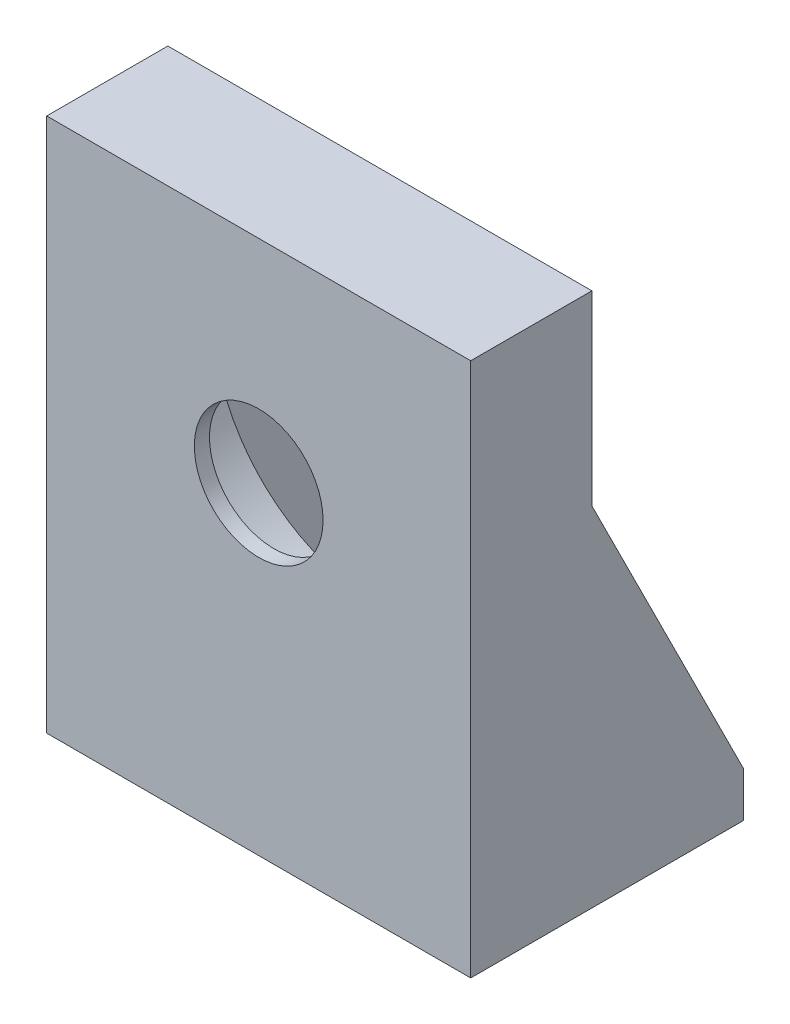
SolidWorks part; units mm, degrees
ref_plane "Front Plane" through (0, 0, 0) normal (0, 0, 1) x (1, 0, 0)
ref_plane "Top Plane" through (0, 0, 0) normal (0, 1, 0) x (1, 0, 0)
ref_plane "Right Plane" through (0, 0, 0) normal (1, 0, 0) x (0, 0, -1)
sketch "Sketch2" plane through (0, 0, -2.5384) normal (0, 0, 1) x (1, 0, 0)
  line L1 (-92.729, 37.136) -> (-64.729, 37.136)
  line L2 (-92.729, 37.136) -> (-92.729, 1.836)
  line L3 (-92.729, 1.836) -> (-64.729, 1.836)
  line L4 (-64.729, 37.136) -> (-64.729, 1.836)
  line L5 (-92.729, 37.136) -> (-64.729, 1.836) construction
  line L6 (-92.729, 1.836) -> (-64.729, 37.136) construction
  line L8 (295.6555, 1.836) -> (-104.3445, 1.836) construction
  line L9 (-78.729, 37.136) -> (-78.729, 1.836) construction
  circle A0 centre (-78.729, 23.136) radius 11
  circle A1 centre (-78.729, 23.136) radius 4.25
  circle A4 centre (-78.729, 23.136) radius 4 construction
  point P11 (-78.729, 19.486)
  circle M1 centre (-78.729, 23.136) radius 9.65
  circle M2 centre (-78.729, 23.136) radius 10.7
  dimension "D1" = 22
  dimension "D2" = 8.5
  dimension "D3" = 14
  dimension "D4" = 14
extrude "Boss-Extrude3" add sketch "Sketch2" against normal up to surface (7 mm away) separate body contours L4 L1 L2 L3 A0 region at (-78.729, 36.6854, -2.5384)
sketch "Sketch3" plane through (-92.729, 0, 0) normal (-1, 0, 0) x (0, 0, 1)
  line L0 (-9.5384, 1.836) -> (-19.5384, 1.836)
  line L1 (-19.5384, 1.836) -> (-19.5384, 4.836)
  line L2 (-19.5384, 4.836) -> (-9.5384, 24.836)
  line L3 (-9.5384, 1.836) -> (-9.5384, 37.136) construction
  line L5 (-19.5384, 4.836) -> (-9.5384, 4.836)
  line L6 (-9.5384, 4.836) -> (-9.5384, 1.836)
  line L7 (-9.5384, 24.836) -> (-9.5384, 4.836)
  line M3 (-9.5384, 37.136) -> (-9.5384, 1.836)
  dimension "D1" = 3
  dimension "D2" = 20
  dimension "D3" = 10
extrude "Boss-Extrude4" add sketch "Sketch3" against normal up to surface (28 mm away) contours L5 L1 L0 M3 region at (-92.729, 3.336, -14.5384) up to face at (-64.729, 19.486, -6.0384)
extrude "Boss-Extrude5" add sketch "Sketch3<3>" against normal blind 3 contours L2 L5 M3 region at (-92.729, 11.5026, -12.8718)
sketch "Sketch3<3>" plane through (-92.729, 0, 0) normal (-1, 0, 0) x (0, 0, 1) same geometry as "Sketch3"
extrude "Boss-Extrude6" add sketch "Sketch3<4>" along normal blind 3 from surface contours L2 L5 M3 region at (-92.729, 11.5026, -12.8718) starting at face at (-64.729, 14.6026, -10.5384)
sketch "Sketch3<4>" plane through (-92.729, 0, 0) normal (-1, 0, 0) x (0, 0, 1) same geometry as "Sketch3"
sketch "Sketch4" plane through (0, 4.836, 0) normal (0, 1, 0) x (1, 0, 0)
  line L0 (-67.729, 14.5384) -> (-89.729, 14.5384) construction
  line L1 (-67.729, 19.5384) -> (-67.729, 9.5384) construction
  line L2 (-89.729, 19.5384) -> (-89.729, 9.5384) construction
  line L3 (-78.729, 9.5384) -> (-78.729, 19.5384) construction
  line L4 (-67.729, 9.5384) -> (-89.729, 9.5384) construction
  line L5 (-67.729, 19.5384) -> (-89.729, 19.5384) construction
  line L6 (-67.729, 14.5384) -> (-78.729, 14.5384) construction
  line L7 (-78.729, 14.5384) -> (-89.729, 14.5384) construction
  circle A0 centre (-72.729, 14.5384) radius 2
  circle A1 centre (-72.729, 14.5384) radius 3.5 construction
  circle A2 centre (-84.729, 14.5384) radius 3.5 construction
  circle A3 centre (-84.729, 14.5384) radius 2
  dimension "D1" = 4
  dimension "D2" = 7
  dimension "D3" = 6
extrude "Cut-Extrude1" cut sketch "Sketch4" against normal through all
extrude "Boss-Extrude7" add sketch "Sketch2<3>" along normal blind 1 contours L4 L1 L2 L3 A0 | A1 M1 | M2 M1 | A0 M2 region at (-78.729, 36.6854, -2.5384) region at (-89.6979, 23.136, -2.5384) region at (-88.1061, 23.136, -2.5384) region at (-89.1264, 23.136, -2.5384)
sketch "Sketch2<3>" plane through (0, 0, -2.5384) normal (0, 0, 1) x (1, 0, 0) same geometry as "Sketch2"
